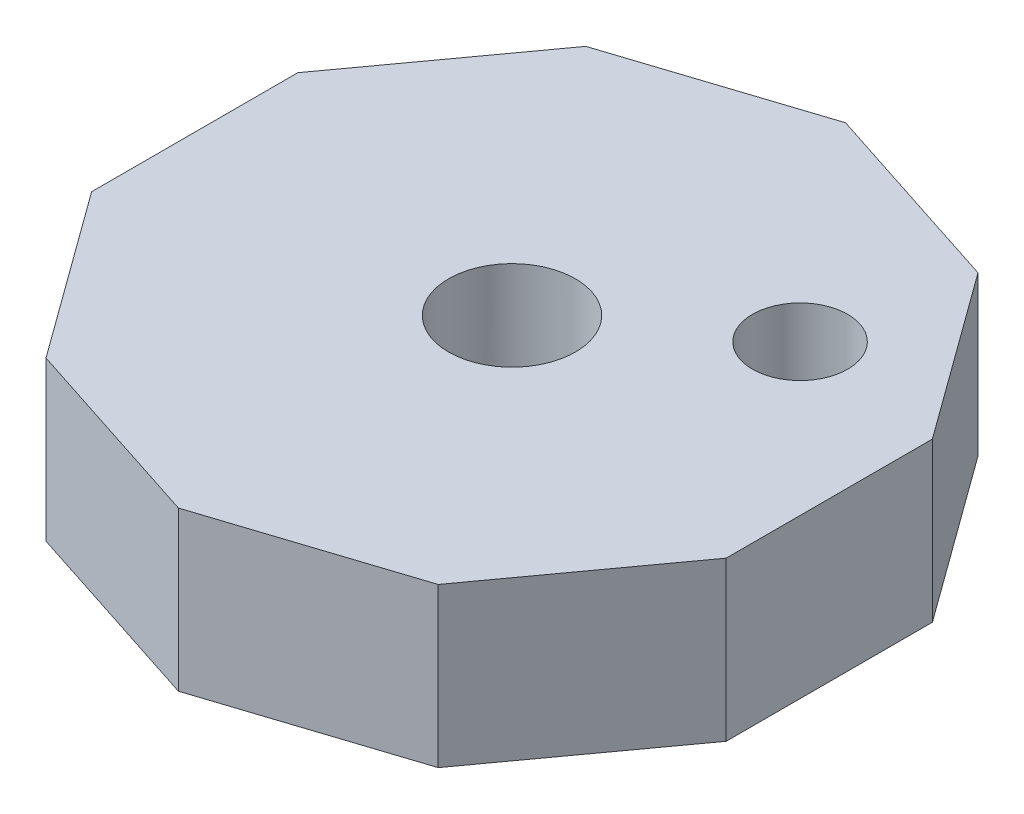
SolidWorks part; units mm, degrees
ref_plane "Front Plane" through (0, 0, 0) normal (0, 0, 1) x (1, 0, 0)
ref_plane "Top Plane" through (0, 0, 0) normal (0, 1, 0) x (1, 0, 0)
ref_plane "Right Plane" through (0, 0, 0) normal (1, 0, 0) x (0, 0, -1)
sketch "Sketch1" plane through (0, 0, 0) normal (0, 1, 0) x (1, 0, 0)
  line L0 (6.1803, -8.5065) -> (10, -3.2492)
  line L1 (0, 10.5146) -> (-6.1803, 8.5065)
  line L2 (-6.1803, 8.5065) -> (-10, 3.2492)
  line L3 (-10, 3.2492) -> (-10, -3.2492)
  line L4 (-10, -3.2492) -> (-6.1803, -8.5065)
  line L5 (-6.1803, -8.5065) -> (0, -10.5146)
  line L6 (0, -10.5146) -> (6.1803, -8.5065)
  line L7 (10, -3.2492) -> (10, 3.2492)
  line L8 (10, 3.2492) -> (6.1803, 8.5065)
  line L9 (6.1803, 8.5065) -> (0, 10.5146)
  circle A0 centre (0, 0) radius 10 construction
  dimension "D1" = 20
extrude "Boss-Extrude1" add sketch "Sketch1" along normal blind 5
sketch "Sketch2" plane through (0, 5, 0) normal (0, 1, 0) x (1, 0, 0)
  line L0 (8.0902, 5.8779) -> (0, 0) construction
  line L1 (10, 3.2492) -> (6.1803, 8.5065) construction
  circle A0 centre (0, 0) radius 2
  circle A1 centre (5.2586, 3.8206) radius 1.5
  dimension "D1" = 4
  dimension "D2" = 3
  dimension "D3" = 3.5
extrude "Cut-Extrude1" cut sketch "Sketch2" against normal blind 5 contours A1 L0 | L0 A1 | A0 region at (5.6328, 5, -3.3056) region at (4.8844, 5, -4.3356)
sketch "Sketch4" plane through (0, 0, 0) normal (0, -1, 0) x (1, 0, 0)
  circle A0 centre (0, 0) radius 3
  dimension "D1" = 6
extrude "Cut-Extrude2" cut sketch "Sketch4" against normal blind 1.5
